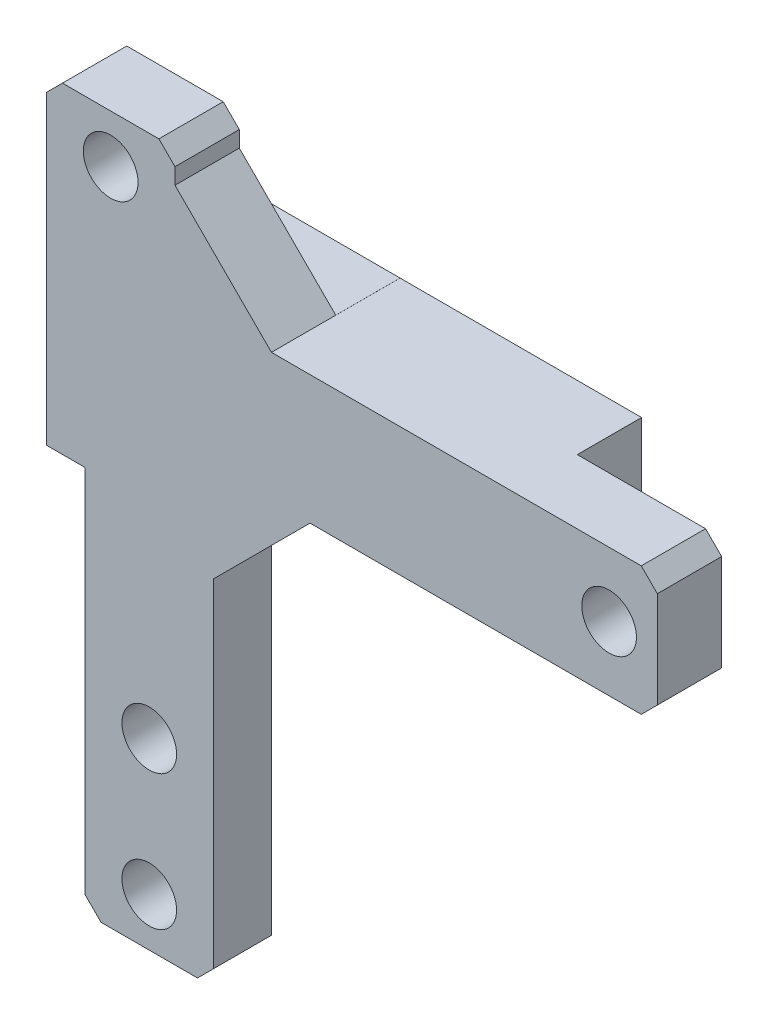
SolidWorks part; units mm, degrees
ref_plane "前视基准面" through (0, 0, 0) normal (0, 0, 1) x (1, 0, 0)
ref_plane "上视基准面" through (0, 0, 0) normal (0, 1, 0) x (1, 0, 0)
ref_plane "右视基准面" through (0, 0, 0) normal (1, 0, 0) x (0, 0, -1)
other "Configuration Table"
sketch "草图1" plane through (0, 0, 0) normal (0, 0, 1) x (1, 0, 0)
  line L0 (-4.3, -2.5) -> (9.5, -2.5)
  line L1 (-5.5, 1.5) -> (9.5, 1.5)
  line L4 (9.5, 1.5) -> (9.5, -2.5)
  line L8 (-9.5, 1.5) -> (-9.5, 5.5)
  line L9 (-9.5, 5.5) -> (-5.5, 5.5)
  line L11 (-5.5, 1.5) -> (-5.5, 5.5)
  line L12 (-9.5, 1.5) -> (-9.5, -4.5)
  line L13 (-8.3, -4.5) -> (-8.3, -16.5)
  line L14 (-8.3, -16.5) -> (-4.3, -16.5)
  line L15 (-4.3, -16.5) -> (-4.3, -2.5)
  line L16 (-9.5, -4.5) -> (-8.3, -4.5)
  circle A0 centre (8, -0.5) radius 0.85
  circle A1 centre (-7.5, 4) radius 0.85
  circle A2 centre (-6.3, -15) radius 0.85
  circle A3 centre (-6.3, -10.8) radius 0.85
  point P0 (0, 0)
  dimension "D16" = 1.7
  dimension "D2" = 6
  dimension "D4" = 2
  dimension "D5" = 1.5
  dimension "D6" = 10
  dimension "D7" = 4
  dimension "D9" = 2
  dimension "D10" = 1.5
  dimension "D11" = 4
  dimension "D12" = 4
  dimension "D13" = 2
  dimension "D14" = 19
  dimension "D17" = 4.2
  dimension "D18" = 1.5
  dimension "D19" = 2
extrude "凸台-拉伸1" add sketch "草图1" along normal blind 4
sketch "草图2" plane through (0, 0, 0) normal (0, 0, 1) x (1, 0, 0)
  line L0 (-8.3, -4.8687) -> (-4.3, -4.8687)
  line L10 (9.5, -2.5) -> (9.5, 1.5)
  line L11 (9.5, 1.5) -> (-5.5, 1.5)
  line L12 (-5.5, 1.5) -> (-5.5, 5.5)
  line L13 (-5.5, 5.5) -> (-9.5, 5.5)
  line L14 (-9.5, 5.5) -> (-9.5, -4.5)
  line L15 (-9.5, -4.5) -> (-8.3, -4.5)
  line L16 (-8.3, -4.5) -> (-8.3, -16.5)
  line L17 (-8.3, -16.5) -> (-4.3, -16.5)
  line L18 (-4.3, -16.5) -> (-4.3, -2.5)
  line L19 (-4.3, -2.5) -> (9.5, -2.5)
  line L26 (-8.3, -4.8687) -> (-8.3, -16.5)
  line L27 (-8.3, -16.5) -> (-4.3, -16.5)
  line L28 (-4.3, -16.5) -> (-4.3, -4.8687)
  circle A0 centre (-6.3, -15) radius 0.85 construction
  circle A1 centre (-6.3, -10.8) radius 0.85 construction
  circle A2 centre (-6.3, -15) radius 0.85
  circle A3 centre (-6.3, -10.8) radius 0.85
  dimension "D2" = 11.6313
  dimension "D1" = 0
extrude "切除-拉伸1" cut sketch "草图2" along normal blind 2.2
sketch "草图3" plane through (0, 0, 0) normal (0, 0, -1) x (-1, 0, 0)
  line L0 (-5.0101, 1.5) -> (-5.0101, -2.5)
  line L1 (5.5, 1.5011) -> (9.5, 1.5011)
  line L10 (-9.5, 1.5) -> (-9.5, -2.5)
  line L11 (-9.5, -2.5) -> (4.3, -2.5)
  line L12 (4.3, -2.5) -> (4.3, -4.8687)
  line L13 (4.3, -4.8687) -> (8.3, -4.8687)
  line L14 (8.3, -4.8687) -> (8.3, -4.5)
  line L15 (8.3, -4.5) -> (9.5, -4.5)
  line L16 (9.5, -4.5) -> (9.5, 5.5)
  line L17 (9.5, 5.5) -> (5.5, 5.5)
  line L18 (5.5, 5.5) -> (5.5, 1.5)
  line L19 (5.5, 1.5) -> (-9.5, 1.5)
  line L20 (-9.5, 1.5) -> (-9.5, -2.5)
  line L21 (-9.5, -2.5) -> (-5.0101, -2.5)
  line L26 (9.5, 1.5011) -> (9.5, 5.5)
  line L27 (9.5, 5.5) -> (5.5, 5.5)
  line L28 (5.5, 5.5) -> (5.5, 1.5011)
  line L29 (-5.0101, 1.5) -> (-9.5, 1.5)
  circle A0 centre (-8, -0.5) radius 0.85 construction
  circle A1 centre (7.5, 4) radius 0.85 construction
  circle A2 centre (-8, -0.5) radius 0.85
  circle A3 centre (7.5, 4) radius 0.85
  dimension "D1" = 0
extrude "切除-拉伸2" cut sketch "草图3" against normal blind 2
chamfer "倒角1" distance 3 angle 45 2 edges at (-4.3, -2.5, 2) (-5.5, 1.5, 2)
chamfer "倒角2" distance 0.5 angle 45 6 edges at (-4.3, -16.5, 3.1) (-8.3, -16.5, 3.1) (-9.5, 5.5, 3) (9.5, -2.5, 3) (9.5, 1.5, 3) (-5.5, 5.5, 3)
